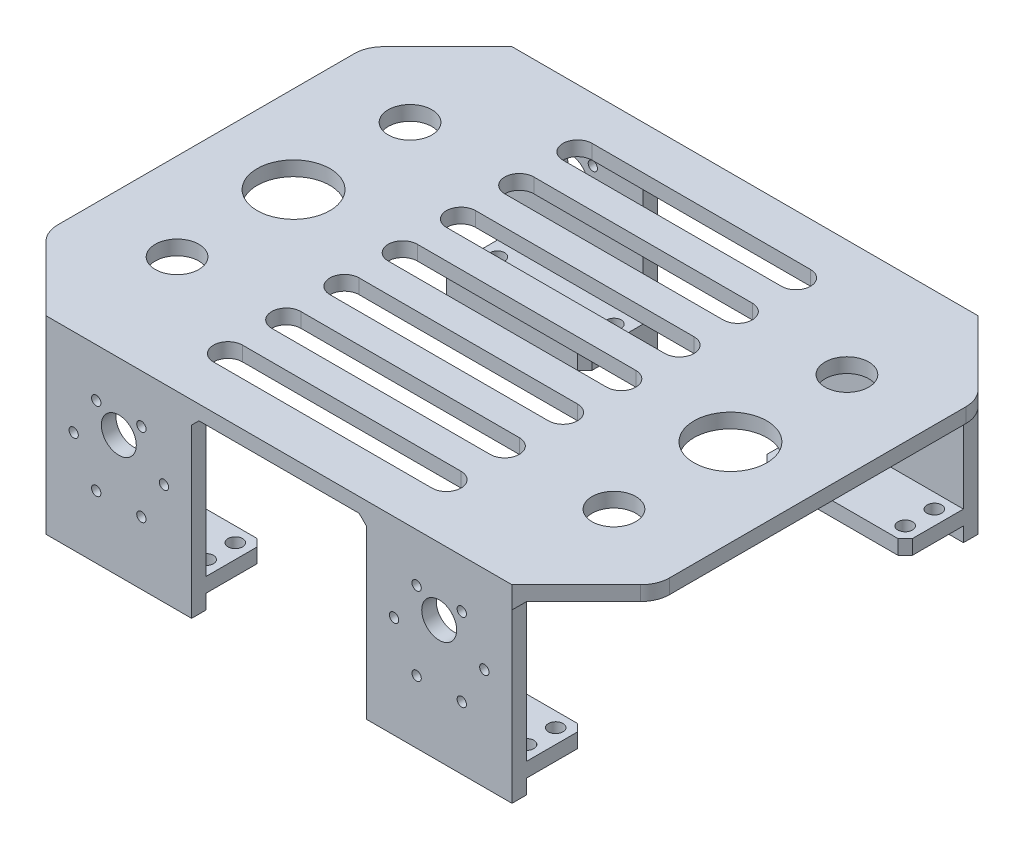
SolidWorks part; units mm, degrees
ref_plane "Front Plane" through (0, 0, 0) normal (0, 0, 1) x (1, 0, 0)
ref_plane "Top Plane" through (0, 0, 0) normal (0, 1, 0) x (1, 0, 0)
ref_plane "Right Plane" through (0, 0, 0) normal (1, 0, 0) x (0, 0, -1)
sketch "Sketch1" plane through (0, 0, 0) normal (0, 0, 1) x (1, 0, 0)
  circle A0 centre (0, 0) radius 18.5
  dimension "D1" = 37
extrude "Boss-Extrude1" add sketch "Sketch1" along normal blind 22.5
sketch "Sketch2" plane through (0, 0, 22.5) normal (0, 0, 1) x (1, 0, 0)
  line L0 (-18.5, 0) -> (18.5, 0) construction
  line L1 (0, 18.5) -> (0, -18.5) construction
  line L2 (11.1332, 19.2832) -> (-10.7359, -18.5952) construction
  line L3 (-11.3747, 19.7016) -> (11.6905, -20.2486) construction
  circle A0 centre (0, 0) radius 18.5 construction
  circle A1 centre (0, 0) radius 15.5 construction
  circle A2 centre (-7.75, 13.4234) radius 1.6
  circle A3 centre (7.75, 13.4234) radius 1.6
  circle A4 centre (-15.5, 0) radius 1.6
  circle A5 centre (-7.75, -13.4234) radius 1.6
  circle A6 centre (7.75, -13.4234) radius 1.6
  circle A7 centre (15.5, 0) radius 1.6
  dimension "D3" = 31
  dimension "D4" = 3.2
  dimension "D1" = 120
  dimension "D2" = 120
extrude "Cut-Extrude1" cut sketch "Sketch2" against normal blind 3.5
sketch "Sketch3" plane through (0, 0, 22.5) normal (0, 0, 1) x (1, 0, 0)
  line L0 (0, 0) -> (0, 18.5) construction
  circle A0 centre (0, 0) radius 18.5 construction
  circle A1 centre (0, 7) radius 6
  circle A2 centre (0, 7) radius 3
  dimension "D1" = 12
  dimension "D3" = 6
  dimension "D2" = 7
extrude "Boss-Extrude2" add sketch "Sketch3" along normal blind 36.3 contours A2 L0 | L0 A2 region at (-1.2732, 7, 22.5) region at (1.2732, 7, 22.5)
extrude "Boss-Extrude3" add sketch "Sketch3<3>" along normal blind 6.3 contours A1 L0 A2 | L0 A1 A2 region at (-5.8658, 7, 22.5) region at (0.1342, 2.5, 22.5)
sketch "Sketch3<3>" plane through (0, 0, 22.5) normal (0, 0, 1) x (1, 0, 0) same geometry as "Sketch3"
sketch "Sketch4" plane through (0, 0, 0) normal (0, 0, -1) x (-1, 0, 0)
  circle A0 centre (0, 0) radius 14.5
  dimension "D1" = 29
extrude "Boss-Extrude4" add sketch "Sketch4" along normal blind 37.8
sketch "Sketch5" plane through (0, 0, -37.8) normal (0, 0, -1) x (-1, 0, 0)
  line L0 (-14.5, 0) -> (14.5, 0) construction
  circle A0 centre (0, 0) radius 5
  circle A1 centre (0, 0) radius 14.5 construction
  dimension "D1" = 10
extrude "Boss-Extrude5" add sketch "Sketch5" along normal blind 3
sketch "Sketch6" plane through (0, 0, -40.8) normal (0, 0, -1) x (-1, 0, 0)
  circle A0 centre (0, 0) radius 1
  dimension "D1" = 2
extrude "Boss-Extrude6" add sketch "Sketch6" along normal blind 9
sketch "Sketch7" plane through (0, 0, -37.8) normal (0, 0, -1) x (-1, 0, 0)
  line L0 (-14.5, 0) -> (14.5, 0) construction
  line L1 (0, 0) -> (0, -10.7163) construction
  line L2 (-12, 1.5) -> (-11.5, 1.5)
  line L3 (-12, 1.5) -> (-12, -1.5)
  line L4 (-12, -1.5) -> (-11.5, -1.5)
  line L5 (-11.5, 1.5) -> (-11.5, -1.5)
  line L6 (12, 1.5) -> (11.5, 1.5)
  line L7 (12, -1.5) -> (11.5, -1.5)
  line L8 (12, 1.5) -> (12, -1.5)
  line L9 (11.5, 1.5) -> (11.5, -1.5)
  circle A0 centre (0, 0) radius 14.5 construction
  circle A1 centre (0, 0) radius 14.5 construction
  dimension "D1" = 3
  dimension "D2" = 1.5
  dimension "D3" = 0.5
  dimension "D4" = 11.5
extrude "Boss-Extrude7" add sketch "Sketch7" along normal blind 6.5
sketch "Sketch8" plane through (12, 0, 0) normal (1, 0, 0) x (0, 0, -1)
  line L0 (42.8651, 0) -> (41.6651, 0) construction
  line L1 (42.8651, -0.3201) -> (41.6651, -0.3201)
  line L2 (42.8651, 0.3201) -> (41.6651, 0.3201)
  line L3 (42.8651, 0) -> (44.3, 0) construction
  line L4 (44.3, 1.5) -> (44.3, -1.5) construction
  arc A0 (42.8651, -0.3201) -> (42.8651, 0.3201) centre (42.8651, 0) ccw
  arc A1 (41.6651, 0.3201) -> (41.6651, -0.3201) centre (41.6651, 0) ccw
  point P2 (42.2651, 0)
  dimension "D1" = 1.2
extrude "Cut-Extrude2" cut sketch "Sketch8" against normal blind 0.5
mirror "Mirror2" about plane through (0, 0, 0) normal (1, 0, 0) of "Cut-Extrude2"
fillet "Fillet1" radius 0.5 4 edges at (-11.75, 1.5, -44.3) (-11.75, -1.5, -44.3) (11.75, 1.5, -44.3) (11.75, -1.5, -44.3)
chamfer "Chamfer1" distance 0.2 angle 45 3 edges at (18.5, 0, 22.5) (6, 7, 28.8) (3, 7, 58.8)
ref_plane "Plane1" through (0, 7, 0) normal (0, 1, 0) x (1, 0, 0)
sketch "Sketch9" plane through (0, 7, 0) normal (0, 1, 0) x (1, 0, 0)
  line L0 (0, -58.6) -> (0, -28.8) construction
  line L1 (3, -58.6) -> (-3, -58.6) construction
  line L2 (-2.8, -58.8) -> (2.8, -58.8) construction
  line L3 (-3, -28.8) -> (3, -28.8) construction
  circle A0 centre (0, -50.8) radius 1.6
  dimension "D1" = 3.2
  dimension "D2" = 8
extrude "Cut-Extrude3" cut sketch "Sketch9" against normal through all and the other way through all
sketch "Sketch10" plane through (0, 0, 22.5) normal (0, 0, 1) x (1, 0, 0)
  circle A0 centre (-7.75, 13.4234) radius 1.6
  circle A1 centre (-15.5, 0) radius 1.6
  circle A2 centre (-7.75, -13.4234) radius 1.6
  circle A3 centre (7.75, -13.4234) radius 1.6
  circle A4 centre (15.5, 0) radius 1.6
  circle A5 centre (7.75, 13.4234) radius 1.6
extrude "Boss-Extrude8" add sketch "Sketch10" along normal blind 10 separate body
sketch "Sketch11" plane through (0, 0, 22.5) normal (0, 0, 1) x (1, 0, 0)
  line L0 (-25, 25) -> (25, 25)
  line L1 (25, 25) -> (25, -35)
  line L2 (25, -35) -> (-25, -35)
  line L3 (-25, -35) -> (-25, 25)
  line L4 (0, -35) -> (0, 25) construction
  dimension "D1" = 60
  dimension "D2" = 50
  dimension "D3" = 50
  dimension "D4" = 25
extrude "Boss-Extrude9" add sketch "Sketch11" along normal blind 5
sketch "Sketch13" plane through (0, 0, 22.5) normal (0, 0, -1) x (-1, 0, 0)
  line L1 (-27.6874, 26.3272) -> (29.1382, 26.3272)
  line L2 (-27.6874, 26.3272) -> (-27.6874, -27.6572)
  line L3 (-27.6874, -27.6572) -> (29.1382, -27.6572)
  line L4 (29.1382, 26.3272) -> (29.1382, -27.6572)
  line L5 (-27.6874, 26.3272) -> (29.1382, -27.6572) construction
  line L6 (-27.6874, -27.6572) -> (29.1382, 26.3272) construction
  point P4 (0.7254, -0.665)
extrude "Cut-Extrude4" cut sketch "Sketch13" along normal blind 121
sketch "Sketch14" plane through (0, 0, 27.5) normal (0, 0, 1) x (1, 0, 0)
  circle A0 centre (-7.75, 13.4234) radius 1.6
  circle A1 centre (7.75, 13.4234) radius 1.6
  circle A2 centre (-15.5, 0) radius 1.6
  circle A3 centre (-7.75, -13.4234) radius 1.6
  circle A4 centre (7.75, -13.4234) radius 1.6
  circle A5 centre (15.5, 0) radius 1.6
  circle A6 centre (0, 7) radius 6
extrude "Cut-Extrude5" cut sketch "Sketch14" against normal through all both and the other way through all
sketch "Sketch15" plane through (0, 25, 0) normal (0, 1, 0) x (1, 0, 0)
  line L1 (-25, -22.5) -> (135, -22.5)
  line L2 (-25, -22.5) -> (-25, -182.5)
  line L3 (-25, -182.5) -> (135, -182.5)
  line L4 (135, -22.5) -> (135, -182.5)
  line L5 (-25, -22.5) -> (135, -182.5) construction
  line L6 (-25, -182.5) -> (135, -22.5) construction
  point P4 (55, -102.5)
  dimension "D1" = 160
  dimension "D2" = 160
extrude "Boss-Extrude10" add sketch "Sketch15" along normal blind 5
sketch "Sketch17" plane through (0, 30, 0) normal (0, 1, 0) x (1, 0, 0)
  line L0 (55, -22.5) -> (55, -182.5) construction
  line L1 (135, -22.5) -> (-25, -22.5) construction
  line L2 (-25, -182.5) -> (135, -182.5) construction
  line L3 (-25, -102.5) -> (135, -102.5) construction
  line L4 (-25, -22.5) -> (-25, -182.5) construction
  line L5 (135, -182.5) -> (135, -22.5) construction
ref_plane "Plane2" through (55, 0, 0) normal (1, 0, 0) x (0, 0, -1)
ref_plane "Plane3" through (0, 0, 102.5) normal (0, 0, 1) x (1, 0, 0)
mirror "Mirror3" about plane through (0, 0, 102.5) normal (0, 0, 1) of bodies 122
mirror "Mirror11" about plane through (55, 0, 0) normal (1, 0, 0) of bodies 123
chamfer "Chamfer2" distance 2.5 angle 45 3 edges at (85, 25, 25) (25, 25, 25) (25, 25, 180)
chamfer "Chamfer3" distance 2.5 angle 45 1 edges at (85, 25, 180)
sketch "Sketch18" plane through (0, 30, 0) normal (0, 1, 0) x (1, 0, 0)
  line L0 (55, -22.5) -> (55, -182.5) construction
  line L1 (135, -22.5) -> (-25, -22.5) construction
  line L2 (-25, -182.5) -> (135, -182.5) construction
  line L3 (17.5, -42.5) -> (92.5, -42.5) construction
  line L4 (17.5, -62.5) -> (92.5, -62.5) construction
  line L5 (17.5, -82.5) -> (92.5, -82.5) construction
  line L6 (17.5, -102.5) -> (92.5, -102.5) construction
  line L7 (17.5, -122.5) -> (92.5, -122.5) construction
  line L8 (17.5, -142.5) -> (92.5, -142.5) construction
  line L9 (92.5, -42.5) -> (17.5, -42.5) construction
  line L10 (92.5, -47.5) -> (17.5, -47.5)
  line L11 (92.5, -37.5) -> (17.5, -37.5)
  line L12 (17.5, -62.5) -> (92.5, -62.5) construction
  line L13 (17.5, -57.5) -> (92.5, -57.5)
  line L14 (17.5, -67.5) -> (92.5, -67.5)
  line L15 (17.5, -82.5) -> (92.5, -82.5) construction
  line L16 (17.5, -77.5) -> (92.5, -77.5)
  line L17 (17.5, -87.5) -> (92.5, -87.5)
  line L18 (17.5, -102.5) -> (92.5, -102.5) construction
  line L19 (17.5, -97.5) -> (92.5, -97.5)
  line L20 (17.5, -107.5) -> (92.5, -107.5)
  line L21 (17.5, -122.5) -> (92.5, -122.5) construction
  line L22 (17.5, -117.5) -> (92.5, -117.5)
  line L23 (17.5, -127.5) -> (92.5, -127.5)
  line L24 (17.5, -142.5) -> (92.5, -142.5) construction
  line L25 (17.5, -137.5) -> (92.5, -137.5)
  line L26 (17.5, -147.5) -> (92.5, -147.5)
  line L27 (17.5, -162.5) -> (92.5, -162.5) construction
  line L28 (92.5, -162.5) -> (17.5, -162.5) construction
  line L29 (92.5, -167.5) -> (17.5, -167.5)
  line L30 (92.5, -157.5) -> (17.5, -157.5)
  arc A0 (92.5, -47.5) -> (92.5, -37.5) centre (92.5, -42.5) ccw
  arc A1 (17.5, -37.5) -> (17.5, -47.5) centre (17.5, -42.5) ccw
  arc A2 (17.5, -57.5) -> (17.5, -67.5) centre (17.5, -62.5) ccw
  arc A3 (92.5, -67.5) -> (92.5, -57.5) centre (92.5, -62.5) ccw
  arc A4 (17.5, -77.5) -> (17.5, -87.5) centre (17.5, -82.5) ccw
  arc A5 (92.5, -87.5) -> (92.5, -77.5) centre (92.5, -82.5) ccw
  arc A6 (17.5, -97.5) -> (17.5, -107.5) centre (17.5, -102.5) ccw
  arc A7 (92.5, -107.5) -> (92.5, -97.5) centre (92.5, -102.5) ccw
  arc A8 (17.5, -117.5) -> (17.5, -127.5) centre (17.5, -122.5) ccw
  arc A9 (92.5, -127.5) -> (92.5, -117.5) centre (92.5, -122.5) ccw
  arc A10 (17.5, -137.5) -> (17.5, -147.5) centre (17.5, -142.5) ccw
  arc A11 (92.5, -147.5) -> (92.5, -137.5) centre (92.5, -142.5) ccw
  arc A12 (92.5, -167.5) -> (92.5, -157.5) centre (92.5, -162.5) ccw
  arc A13 (17.5, -157.5) -> (17.5, -167.5) centre (17.5, -162.5) ccw
  point P14 (55, -42.5)
  point P15 (55, -62.5)
  point P16 (55, -82.5)
  point P17 (55, -122.5)
  point P20 (55, -102.5)
  point P23 (55, -142.5)
  point P24 (55, -42.5)
  point P29 (55, -62.5)
  point P34 (55, -82.5)
  point P39 (55, -102.5)
  point P44 (55, -122.5)
  point P49 (55, -142.5)
  point P54 (55, -162.5)
  point P56 (55, -162.5)
  dimension "D2" = 5
  dimension "D3" = 5
  dimension "D4" = 5
  dimension "D5" = 5
  dimension "D7" = 5
  dimension "D8" = 5
  dimension "D14" = 5
  dimension "D1" = 75
  dimension "D6" = 20
  dimension "D9" = 20
  dimension "D10" = 20
  dimension "D11" = 20
  dimension "D12" = 20
  dimension "D13" = 20
  dimension "D15" = 20
extrude "Cut-Extrude6" cut sketch "Sketch18" against normal through all
sketch "Sketch19" plane through (0, 30, 0) normal (0, 1, 0) x (1, 0, 0)
  line L0 (-25, -182.5) -> (135, -182.5) construction
  line L1 (-25, -22.5) -> (-50, -22.5)
  line L2 (-25, -22.5) -> (-25, -182.5)
  line L3 (-25, -182.5) -> (-50, -182.5)
  line L4 (-50, -22.5) -> (-50, -182.5)
  line L5 (-25, -22.5) -> (-50, -182.5) construction
  line L6 (-25, -182.5) -> (-50, -22.5) construction
  line L8 (135, -22.5) -> (160, -22.5)
  line L9 (135, -22.5) -> (135, -182.5)
  line L10 (135, -182.5) -> (160, -182.5)
  line L11 (160, -22.5) -> (160, -182.5)
  line L12 (135, -22.5) -> (160, -182.5) construction
  line L13 (135, -182.5) -> (160, -22.5) construction
  point P4 (-37.5, -102.5)
  point P12 (147.5, -102.5)
  dimension "D1" = 25
extrude "Boss-Extrude11" add sketch "Sketch19" against normal up to surface (5 mm away) up to face at (55, 25, 42.5)
chamfer "Chamfer4" distance 25 angle 45 4 edges at (-50, 27.5, 22.5) (-50, 27.5, 182.5) (160, 27.5, 182.5) (160, 27.5, 22.5)
sketch "Sketch20" plane through (0, 30, 0) normal (0, 1, 0) x (1, 0, 0)
  line L0 (55, -22.5) -> (55, -182.5) construction
  line L1 (135, -22.5) -> (-25, -22.5) construction
  line L2 (-25, -182.5) -> (135, -182.5) construction
  line L3 (-50, -102.5) -> (160, -102.5) construction
  line L4 (-50, -47.5) -> (-50, -157.5) construction
  line L5 (160, -157.5) -> (160, -47.5) construction
  circle A0 centre (130, -102.5) radius 12.5
  circle A1 centre (130, -62.5) radius 7.5
  circle A2 centre (130, -142.5) radius 7.5
  circle A3 centre (-20, -142.5) radius 7.5
  circle A4 centre (-20, -102.5) radius 12.5
  circle A5 centre (-20, -62.5) radius 7.5
  point P26 (55, -102.5)
  dimension "D3" = 25
  dimension "D4" = 15
  dimension "D1" = 75
  dimension "D2" = 40
extrude "Cut-Extrude7" cut sketch "Sketch20" against normal blind 10
chamfer "Chamfer5" distance 2.5 angle 45 4 edges at (108.75, 25, 177.5) (1.25, 25, 177.5) (1.25, 25, 27.5) (108.75, 25, 27.5)
chamfer "Chamfer6" distance 2.5 angle 45 4 edges at (135, 25, 178.75) (135, 25, 26.25) (-25, 25, 26.25) (-25, 25, 178.75)
fillet "Fillet2" radius 10 4 edges at (-50, 27.5, 157.5) (-50, 27.5, 47.5) (160, 27.5, 47.5) (160, 27.5, 157.5)
sketch "Sketch21" plane through (0, -35, 0) normal (0, -1, 0) x (1, 0, 0)
  line L0 (135, 27.5) -> (135, 22.5) construction
  line L1 (85, 27.5) -> (135, 27.5)
  line L2 (85, 27.5) -> (85, 47.5)
  line L3 (85, 47.5) -> (135, 47.5)
  line L4 (135, 27.5) -> (135, 47.5)
  line L5 (85, 27.5) -> (135, 47.5) construction
  line L6 (85, 47.5) -> (135, 27.5) construction
  line L7 (55, 22.5) -> (55, 152.5338) construction
  line L8 (82.5, 22.5) -> (27.5, 22.5) construction
  line L9 (-50, 102.5) -> (115.8543, 102.5) construction
  line L10 (-50, 153.3579) -> (-50, 51.6421) construction
  line L11 (110, 37.5) -> (110, 45.6589) construction
  line L12 (110, 37.5) -> (99.3164, 37.5) construction
  line L13 (85, 157.5) -> (135, 157.5)
  line L14 (135, 177.5) -> (135, 157.5)
  line L15 (85, 177.5) -> (135, 177.5)
  line L16 (85, 177.5) -> (85, 157.5)
  line L17 (25, 177.5) -> (-25, 177.5)
  line L18 (25, 177.5) -> (25, 157.5)
  line L19 (25, 157.5) -> (-25, 157.5)
  line L20 (-25, 177.5) -> (-25, 157.5)
  line L21 (-25, 27.5) -> (-25, 47.5)
  line L22 (25, 27.5) -> (-25, 27.5)
  line L23 (25, 47.5) -> (-25, 47.5)
  line L24 (25, 27.5) -> (25, 47.5)
  circle A0 centre (90, 32.5) radius 2.5
  circle A1 centre (90, 42.5) radius 2.5
  circle A2 centre (130, 32.5) radius 2.5
  circle A3 centre (130, 42.5) radius 2.5
  circle A4 centre (90, 162.5) radius 2.5
  circle A5 centre (90, 172.5) radius 2.5
  circle A6 centre (130, 172.5) radius 2.5
  circle A7 centre (130, 162.5) radius 2.5
  circle A8 centre (-20, 162.5) radius 2.5
  circle A9 centre (-20, 172.5) radius 2.5
  circle A10 centre (20, 172.5) radius 2.5
  circle A11 centre (20, 162.5) radius 2.5
  circle A12 centre (-20, 32.5) radius 2.5
  circle A13 centre (-20, 42.5) radius 2.5
  circle A14 centre (20, 32.5) radius 2.5
  circle A15 centre (20, 42.5) radius 2.5
  point P4 (110, 37.5)
  dimension "D4" = 5
  dimension "D1" = 20
  dimension "D2" = 5
  dimension "D3" = 20
extrude "Boss-Extrude12" add sketch "Sketch21" against normal blind 5 from offset 5 offset against normal yes
chamfer "Chamfer7" distance 2.5 angle 45 8 edges at (85, -27.5, 47.5) (135, -27.5, 47.5) (-25, -27.5, 47.5) (25, -27.5, 47.5) (25, -27.5, 157.5) (-25, -27.5, 157.5) (85, -27.5, 157.5) (135, -27.5, 157.5)
